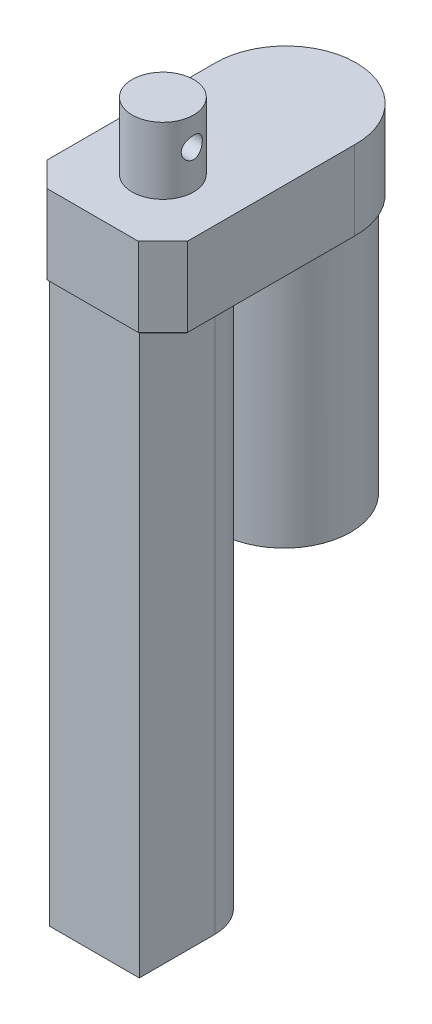
SolidWorks part; units mm, degrees
ref_plane "Alzado" through (0, 0, 0) normal (0, 0, 1) x (1, 0, 0)
ref_plane "Planta" through (0, 0, 0) normal (0, 1, 0) x (1, 0, 0)
ref_plane "Vista lateral" through (0, 0, 0) normal (1, 0, 0) x (0, 0, -1)
sketch "Croquis1" plane through (0, 0, 0) normal (0, 1, 0) x (1, 0, 0)
  line L0 (0, -27.25) -> (0, 47.75) construction
  line L1 (-20, -27.25) -> (20, -27.25)
  line L2 (-20, -27.25) -> (-20, 27.25)
  line L4 (20, -27.25) -> (20, 27.25)
  line L5 (-20, -27.25) -> (20, 27.25) construction
  line L6 (-20, 27.25) -> (20, -27.25) construction
  arc A1 (20, 27.25) -> (-20, 27.25) centre (0, 27.7439) ccw
  point P0 (0, 0)
  dimension "D1" = 40
  dimension "D2" = 54.5
  dimension "D3" = 75
extrude "Saliente-Extruir1" add sketch "Croquis1" along normal blind 23
chamfer "Chaflán1" distance 7 angle 45 2 edges at (20, 11.5, 27.25) (-20, 11.5, 27.25)
sketch "Croquis2" plane through (0, 23, 0) normal (0, 1, 0) x (1, 0, 0)
  line L0 (-13, -27.25) -> (13, -27.25) construction
  circle A0 centre (0, -7.25) radius 8.75
  dimension "D1" = 17.5
  dimension "D2" = 20
extrude "Saliente-Extruir2" add sketch "Croquis2" along normal blind 19
chamfer "Chaflán2" distance 0.5 angle 45 6 edges at (0, 0, -47.75) (-20, 0, -3.5) (-16.5, 0, 23.75) (0, 0, 27.25) (16.5, 0, 23.75) (20, 0, -3.5)
sketch "Croquis4" plane through (0, 0, 0) normal (0, -1, 0) x (1, 0, 0)
  circle A0 centre (0, -27.25) radius 19
  circle A2 centre (0, 7.25) radius 8.75
  circle A3 centre (0, 7.25) radius 8.75 construction
  dimension "D1" = 38
  dimension "D3" = 34.5
  dimension "D2" = 0
extrude "Saliente-Extruir3" add sketch "Croquis4" along normal blind 73
sketch "Croquis3" plane through (0, 0, 0) normal (1, 0, 0) x (0, 0, -1)
  line L0 (-27.25, 0.5) -> (-27.25, 23) construction
  line L1 (1.5, 42) -> (-16, 42) construction
  circle A0 centre (-7.25, 34) radius 3
  dimension "D1" = 6
  dimension "D2" = 20
  dimension "D3" = 8
extrude "Cortar-Extruir1" cut sketch "Croquis3" against normal mid plane 25
sketch "Croquis5" plane through (0, 0, 0) normal (0, -1, 0) x (1, 0, 0)
  line L0 (-12.7929, 26.75) -> (-12.7929, 5.25)
  line L1 (12.7929, 5.25) -> (12.7929, 26.75)
  line L5 (-19.5, 20.0429) -> (-19.5, -27.2562)
  line L6 (19.5, -27.2562) -> (19.5, 20.0429)
  line L7 (19.5, 20.0429) -> (12.7929, 26.75)
  line L8 (12.7929, 26.75) -> (-12.7929, 26.75)
  line L9 (-12.7929, 26.75) -> (-19.5, 20.0429)
  line L10 (-19.5, 20.0429) -> (-19.5, -27.2562)
  line L11 (19.5, -27.2562) -> (19.5, 20.0429)
  line L12 (19.5, 20.0429) -> (12.7929, 26.75)
  line L13 (12.7929, 26.75) -> (-12.7929, 26.75)
  line L14 (-12.7929, 26.75) -> (-19.5, 20.0429)
  arc A0 (-12.7929, 5.25) -> (12.7929, 5.25) centre (0, 5.25) ccw
  arc A1 (-19.5, -27.2562) -> (19.5, -27.2562) centre (0, -27.7439) ccw
  arc A2 (-19.5, -27.2562) -> (19.5, -27.2562) centre (0, -27.7439) ccw
  line M12 (12.7929, 26.75) -> (-12.7929, 26.75)
  dimension "D2" = 21.5
  dimension "D1" = 0
extrude "Saliente-Extruir7" add sketch "Croquis5" along normal blind 159 contours L0 A0 L1 M12 region at (0, 0, 10.847)
sketch "Croquis6" plane through (0, -159, 0) normal (0, -1, 0) x (1, 0, 0)
  circle A0 centre (0, 7.25) radius 10
  circle A1 centre (0, 7.25) radius 8.75
  circle A2 centre (0, 7.25) radius 8.75 construction
  dimension "D1" = 0
extrude "Cortar-Extruir2" cut sketch "Croquis6" against normal blind 100
ref_point "Point1"
